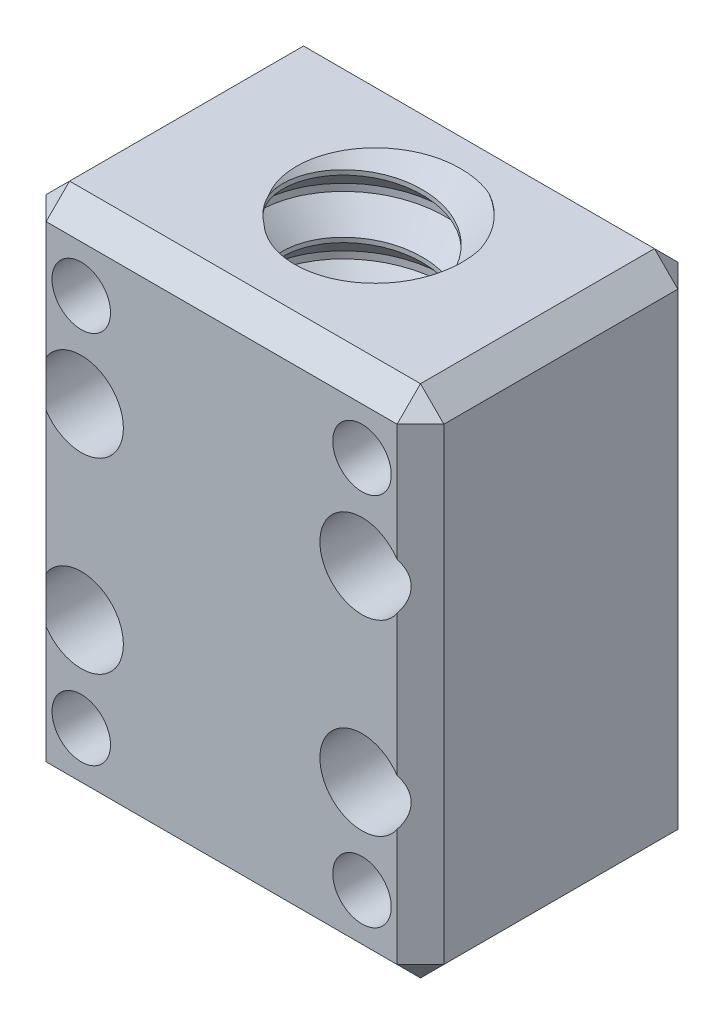
SolidWorks part; units mm, degrees
ref_plane "前视基准面" through (0, 0, 0) normal (0, 0, 1) x (1, 0, 0)
ref_plane "上视基准面" through (0, 0, 0) normal (0, 1, 0) x (1, 0, 0)
ref_plane "右视基准面" through (0, 0, 0) normal (1, 0, 0) x (0, 0, -1)
sketch "草图1" plane through (0, 0, 0) normal (0, 0, 1) x (1, 0, 0)
  line L1 (-8.5, -11) -> (8.5, -11)
  line L2 (-8.5, -11) -> (-8.5, 11)
  line L3 (-8.5, 11) -> (8.5, 11)
  line L4 (8.5, -11) -> (8.5, 11)
  line L5 (-8.5, -11) -> (8.5, 11) construction
  line L6 (-8.5, 11) -> (8.5, -11) construction
  point P0 (0, 0)
  dimension "D1" = 17
  dimension "D2" = 22
extrude "凸台-拉伸1" add sketch "草图1" along normal blind 12
sketch "草图2" plane through (0, -11, 0) normal (0, -1, 0) x (1, 0, 0)
  line L0 (-8.5, 6) -> (8.5, 6) construction
  line L1 (-8.5, 12) -> (-8.5, 0) construction
  line L2 (8.5, 12) -> (8.5, 0) construction
  line L3 (0, 0) -> (0, 12) construction
  line L4 (-8.5, 12) -> (8.5, 12) construction
  circle A0 centre (0, 6) radius 4
  dimension "D1" = 8
extrude "切除-拉伸1" cut sketch "草图2" against normal up to next
sketch "草图3" plane through (0, -11, 0) normal (0, -1, 0) x (1, 0, 0)
  circle A0 centre (0, 6) radius 4 construction
  circle A1 centre (0, 6) radius 4
curve "螺旋线/涡状线1" pitch 2.5 height 22.5 radius 4 centre (0, -11, 6) axis (0, 1, 0) start towards (0, 0, -1)
sketch "草图6" plane through (0, 0, 0) normal (1, 0, 0) x (0, 0, -1)
  line L0 (-2, -8.8) -> (-2, -11)
  line L1 (-2, -11) -> (-3, -10)
  line L2 (-3, -10) -> (-3, -9.8)
  line L3 (-3, -9.8) -> (-2, -8.8)
  point P2 (-3, -9.9)
  point P5 (-2, -9.9)
  dimension "D1" = 2.2
  dimension "D2" = 1
  dimension "D3" = 45
sweep "扫描1" add profiles "草图6" path "螺旋线/涡状线1"
sketch "草图7" plane through (0, 11, 0) normal (0, 1, 0) x (1, 0, 0)
  circle A0 centre (0, -6) radius 15.4839
extrude "切除-拉伸3" cut sketch "草图7" along normal blind 30
sketch "草图8" plane through (0, 0, 12) normal (0, 0, 1) x (1, 0, 0)
  line L0 (-14.8745, 4) -> (15.9779, 4) construction
  line L1 (0, 6.1723) -> (0, -6.7506) construction
  line L2 (-2.9516, 0) -> (3.5387, 0) construction
  line L3 (0, -6.1723) -> (0, 6.7506) construction
  line L4 (-14.8745, -4) -> (15.9779, -4) construction
  circle A0 centre (6, 4) radius 1.1
  circle A1 centre (-6, 4) radius 1.1
  circle A2 centre (-6, -4) radius 1.1
  circle A3 centre (6, -4) radius 1.1
  dimension "D1" = 2.2
  dimension "D2" = 12
  dimension "D3" = 8
extrude "切除-拉伸4" cut sketch "草图8" against normal through all
sketch "草图9" plane through (0, 0, 12) normal (0, 0, 1) x (1, 0, 0)
  circle A0 centre (-6, 4) radius 1.8
  circle A1 centre (6, 4) radius 1.8
  circle A2 centre (6, -4) radius 1.8
  circle A3 centre (-6, -4) radius 1.8
  dimension "D1" = 3.6
  dimension "D2" = 3.6
  dimension "D3" = 3.6
  dimension "D4" = 3.6
extrude "切除-拉伸5" cut sketch "草图9" against normal blind 7
sketch "草图10" plane through (0, 0, 12) normal (0, 0, 1) x (1, 0, 0)
  line L0 (-9.8772, 0) -> (10.0907, 0) construction
  line L1 (0, 11.8176) -> (0, -11.5673) construction
  circle A0 centre (6, 8) radius 1.25
  circle A1 centre (-6, 8) radius 1.25
  circle A2 centre (6, -8) radius 1.25
  circle A3 centre (-6, -8) radius 1.25
  dimension "D1" = 2.5
  dimension "D2" = 8
  dimension "D3" = 6
extrude "切除-拉伸6" cut sketch "草图10" against normal blind 7
fillet "圆角1" radius 1 12 edges at (8.5, -11, 6) (8.5, 11, 6) (0, 11, 0) (0, -11, 0) (8.5, 0, 0) (0, -11, 12) (0, 11, 12) (8.5, 0, 12) (-8.5, 11, 6) (-8.5, 0, 12) (-8.5, -11, 6) (-8.5, 0, 0) profile chamfer
